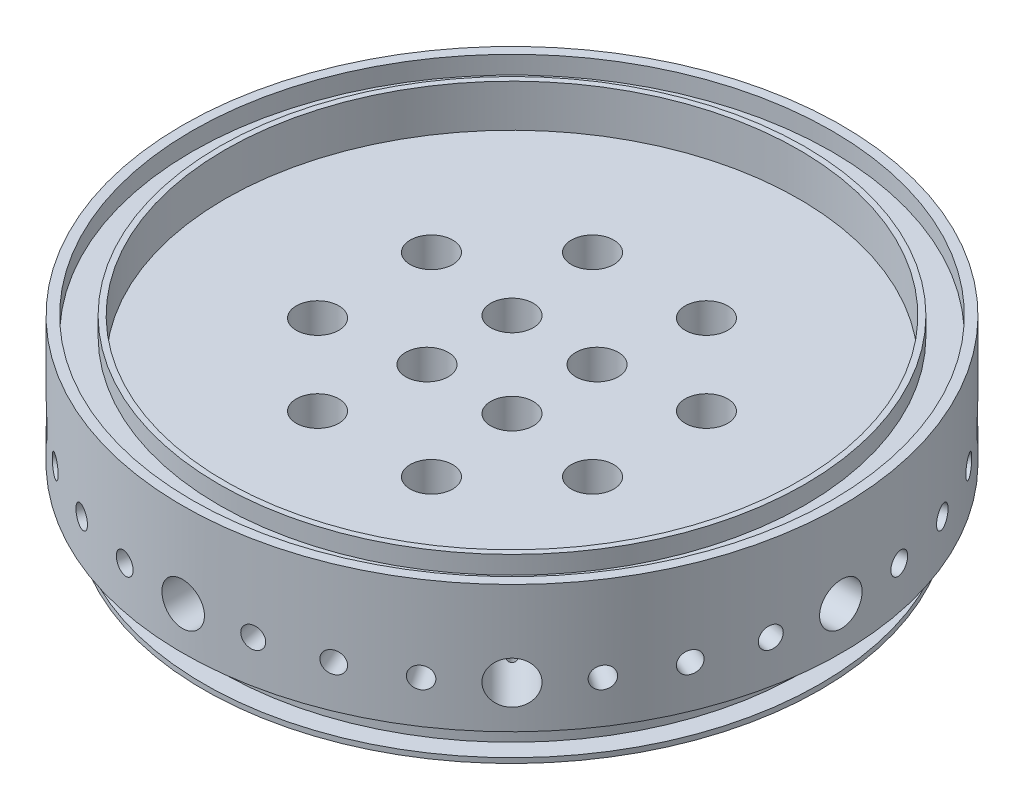
SolidWorks part; units mm, degrees
material "6061-T4 (SS)"
ref_plane "Front Plane" through (0, 0, 0) normal (0, 0, 1) x (1, 0, 0)
ref_plane "Top Plane" through (0, 0, 0) normal (0, 1, 0) x (1, 0, 0)
ref_plane "Right Plane" through (0, 0, 0) normal (1, 0, 0) x (0, 0, -1)
ref_axis "Axis1" through (0, -42.3, 0) along (0, 1, 0)
sketch "Sketch1" plane through (0, 0, 0) normal (0, 0, 1) x (1, 0, 0)
  line L0 (0, 0) -> (-46.0375, 0)
  line L1 (-46.0375, 0) -> (-46.0375, 0.7556)
  line L2 (-46.0375, 0.7556) -> (-43.2181, 0.7556)
  line L3 (-43.2181, 0.7556) -> (-43.2181, 5.5562)
  line L4 (-43.2181, 5.5562) -> (-46.0375, 5.5562)
  line L5 (-46.0375, 5.5562) -> (-46.0375, 6.35)
  line L6 (-46.0375, 6.35) -> (-49.2125, 6.35)
  line L7 (-49.2125, 6.35) -> (-49.2125, 25.4)
  line L10 (-42.8625, 19.05) -> (0, 19.05)
  line L11 (0, 19.05) -> (0, 0)
  line L12 (-42.8625, 19.05) -> (-42.8625, 25.4)
  line L15 (-49.2125, 25.4) -> (-47.7774, 25.4)
  line L16 (-47.7774, 25.4) -> (-47.7774, 22.7076)
  line L17 (-47.7774, 22.7076) -> (-43.7134, 22.7076)
  line L18 (-43.7134, 22.7076) -> (-43.7134, 25.4)
  line L19 (-43.7134, 25.4) -> (-42.8625, 25.4)
  dimension "D1" = 46.0375
  dimension "D2" = 4.8006
  dimension "D3" = 19.05
  dimension "D4" = 0.7937
  dimension "D6" = 3.175
  dimension "D7" = 6.35
  dimension "D9" = 19.05
  dimension "D10" = 4.064
  dimension "D11" = 2.6924
  dimension "D12" = 6.35
  dimension "o-ring -238" = 47.7774
  dimension "o-ring -" = 43.2181
revolve "Revolve1" add sketch "Sketch1" angle 360 about L11
ref_plane "Plane1" through (49.2125, 0, 0) normal (1, 0, 0) x (0, 0, -1)
hole_wizard "1/8 (0.125) Diameter Hole2" positions "Sketch36" profile "Sketch37" hole size "1/8" standard "ANSI Inch"
sketch "Sketch36" plane through (49.2125, 0, 0) normal (1, 0, 0) x (0, 0, -1)
  line L0 (0, 13.97) -> (0, -13.97) construction
  point P0 (0, 12.7)
  dimension "D1" = 12.7
sketch "Sketch37" plane through (49.2125, 12.7, 0) normal (0, 1, 0) x (0, 0, -1)
  line L0 (0, 0) -> (0, 13.6539)
  line L1 (0, 13.6539) -> (1.5875, 12.7)
  line L2 (1.5875, 12.7) -> (1.5875, 0)
  line L5 (1.5875, 0) -> (0, 0)
  line L10 (0, 13.6539) -> (-1.5875, 12.7) construction
  line L11 (0, -6.35) -> (0, 107.95) construction
  dimension "Hole Dia." = 3.175
  dimension "Hole Depth" = 12.7
  dimension "Drill Angle" = 118
pattern_circular "CirPattern9" count 32 over 360 about axis through (0, -42.3, 0) along (0, 1, 0) of "1/8 (0.125) Diameter Hole2"
hole_wizard "1/4 (0.25) Diameter Hole1" positions "Sketch12" profile "Sketch13" hole size "1/4" standard "ANSI Inch"
sketch "Sketch12" plane through (49.2125, 0, 0) normal (1, 0, 0) x (0, 0, -1)
  point P0 (0, 12.7)
  dimension "D1" = 12.7
sketch "Sketch13" plane through (49.2125, 12.7, 0) normal (0, 1, 0) x (0, 0, -1)
  line L0 (0, 0) -> (0, 14.6077)
  line L1 (0, 14.6077) -> (3.175, 12.7)
  line L2 (3.175, 12.7) -> (3.175, 0)
  line L5 (3.175, 0) -> (0, 0)
  line L10 (0, 14.6077) -> (-3.175, 12.7) construction
  line L11 (0, -6.35) -> (0, 107.95) construction
  dimension "Hole Dia." = 6.35
  dimension "Hole Depth" = 12.7
  dimension "Drill Angle" = 118
hole_wizard "3/16 (0.1875) Diameter Hole1" positions "Sketch14" profile "Sketch15" hole size "3/16" standard "ANSI Inch"
sketch "Sketch14" plane through (49.2125, 0, 0) normal (1, 0, 0) x (0, 0, -1)
  point P0 (0, 12.7)
sketch "Sketch15" plane through (49.2125, 12.7, 0) normal (0, 1, 0) x (0, 0, -1)
  line L0 (0, 0) -> (0, 33.1808)
  line L1 (0, 33.1808) -> (2.3812, 31.75)
  line L2 (2.3812, 31.75) -> (2.3812, 0)
  line L5 (2.3812, 0) -> (0, 0)
  line L10 (0, 33.1808) -> (-2.3813, 31.75) construction
  line L11 (0, -6.35) -> (0, 107.95) construction
  dimension "Hole Dia." = 4.7625
  dimension "Hole Depth" = 31.75
  dimension "Drill Angle" = 118
hole_wizard "1/8 (0.125) Diameter Hole1" positions "Sketch16" profile "Sketch17" hole size "1/8" standard "ANSI Inch"
sketch "Sketch16" plane through (49.2125, 0, 0) normal (1, 0, 0) x (0, 0, -1)
  point P0 (0, 12.7)
sketch "Sketch17" plane through (49.2125, 12.7, 0) normal (0, 1, 0) x (0, 0, -1)
  line L0 (0, 0) -> (0, 45.4039)
  line L1 (0, 45.4039) -> (1.5875, 44.45)
  line L2 (1.5875, 44.45) -> (1.5875, 0)
  line L5 (1.5875, 0) -> (0, 0)
  line L10 (0, 45.4039) -> (-1.5875, 44.45) construction
  line L11 (0, -6.35) -> (0, 107.95) construction
  dimension "Hole Dia." = 3.175
  dimension "Hole Depth" = 44.45
  dimension "Drill Angle" = 118
pattern_circular "CirPattern1" count 8 over 360 about axis through (0, -42.3, 0) along (0, 1, 0) of "1/4 (0.25) Diameter Hole1"
pattern_circular "CirPattern2" count 8 over 360 about axis through (0, -42.3, 0) along (0, 1, 0) of "3/16 (0.1875) Diameter Hole1"
pattern_circular "CirPattern3" count 4 over 360 about axis through (0, -42.3, 0) along (0, 1, 0) of "1/8 (0.125) Diameter Hole1"
ref_plane "Plane2" through (0, 19.05, 0) normal (0, 1, 0) x (1, 0, 0)
hole_wizard "inner large LOX holes" positions "Sketch19" profile "Sketch20" hole size "1/4" standard "ANSI Inch"
sketch "Sketch19" plane through (0, 19.05, 0) normal (0, 1, 0) x (1, 0, 0)
  line L2 (-6.35, 0) -> (0, 0) construction
  line L4 (-6.35, -6.35) -> (-6.35, 0) construction
  point P0 (-6.35, -6.35)
  dimension "D1" = 6.35
  dimension "D2" = 6.35
sketch "Sketch20" plane through (-6.35, 19.05, 6.35) normal (1, 0, 0) x (0, 0, 1)
  line L0 (0, 0) -> (0, 14.6077)
  line L1 (0, 14.6077) -> (3.175, 12.7)
  line L2 (3.175, 12.7) -> (3.175, 0)
  line L5 (3.175, 0) -> (0, 0)
  line L10 (0, 14.6077) -> (-3.175, 12.7) construction
  line L11 (0, -6.35) -> (0, 107.95) construction
  dimension "Hole Dia." = 6.35
  dimension "Hole Depth" = 12.7
  dimension "Drill Angle" = 118
hole_wizard "outer large LOX hole" positions "Sketch21" profile "Sketch22" hole size "1/4" standard "ANSI Inch"
sketch "Sketch21" plane through (0, 19.05, 0) normal (0, 1, 0) x (1, 0, 0)
  line L0 (-20.5332, -8.5051) -> (0, 0) construction
  line L2 (0, 0) -> (-17.5003, 0) construction
  point P0 (-20.5332, -8.5051)
  dimension "D1" = 22.5
  dimension "D2" = 22.225
sketch "Sketch22" plane through (-20.5332, 19.05, 8.5051) normal (1, 0, 0) x (0, 0, 1)
  line L0 (0, 0) -> (0, 14.6077)
  line L1 (0, 14.6077) -> (3.175, 12.7)
  line L2 (3.175, 12.7) -> (3.175, 0)
  line L5 (3.175, 0) -> (0, 0)
  line L10 (0, 14.6077) -> (-3.175, 12.7) construction
  line L11 (0, -6.35) -> (0, 107.95) construction
  dimension "Hole Dia." = 6.35
  dimension "Hole Depth" = 12.7
  dimension "Drill Angle" = 118
pattern_circular "CirPattern4" count 4 over 360 about axis through (0, -42.3, 0) along (0, 1, 0) of "inner large LOX holes"
pattern_circular "CirPattern5" count 8 over 360 about axis through (0, -42.3, 0) along (0, 1, 0) of "outer large LOX hole"
ref_plane "Plane4" through (-41.275, 0, 0) normal (1, 0, 0) x (0, 0, -1)
ref_axis "Axis4" through (-41.275, 0, -54.1338) along (0, 0, 1)
ref_plane "Plane5" through (-0.3135, -3.5837, 0) normal (0.0872, 0.9962, 0) x (0, 0, 1)
ref_plane "Plane6" through (-0.4519, -5.1651, 0) normal (0.0872, 0.9962, 0) x (0, 0, 1)
hole_wizard "film cooling holes" positions "Sketch25" profile "Sketch26" hole size "#74" standard "ANSI Inch"
sketch "Sketch25" plane through (-0.4519, -5.1651, 0) normal (0.0872, 0.9962, 0) x (0, 0, 1)
  line L0 (0, -41.1179) -> (0, 0) construction
  line L1 (-54.1338, -41.1179) -> (54.1338, -41.1179) construction
  point P0 (0, -41.1179)
sketch "Sketch26" plane through (-41.4134, -1.5815, 0) normal (0, 0, 1) x (0.9962, -0.0872, 0)
  line L0 (0, 0) -> (0, 12.8717)
  line L1 (0, 12.8717) -> (0.2857, 12.7)
  line L2 (0.2857, 12.7) -> (0.2857, 0)
  line L5 (0.2857, 0) -> (0, 0)
  line L10 (0, 12.8717) -> (-0.2858, 12.7) construction
  line L11 (0, -6.35) -> (0, 107.95) construction
  dimension "Hole Dia." = 0.5715
  dimension "Hole Depth" = 12.7
  dimension "Drill Angle" = 118
pattern_circular "CirPattern6" count 32 over 360 about axis through (0, -42.3, 0) along (0, 1, 0) of "film cooling holes"
hole_wizard "3/64 (0.04688) Diameter Hole1" positions "Sketch38" profile "Sketch39" hole size "3/64" standard "ANSI Inch"
sketch "Sketch38" plane through (-0.4519, -5.1651, 0) normal (0.0872, 0.9962, 0) x (0, 0, 1)
  point P0 (0, -41.1179)
sketch "Sketch39" plane through (-41.4134, -1.5815, 0) normal (0, 0, 1) x (0.9962, -0.0872, 0)
  line L0 (0, 0) -> (0, 13.0577)
  line L1 (0, 13.0577) -> (0.5954, 12.7)
  line L2 (0.5954, 12.7) -> (0.5954, 0)
  line L5 (0.5954, 0) -> (0, 0)
  line L10 (0, 13.0577) -> (-0.5954, 12.7) construction
  line L11 (0, -6.35) -> (0, 107.95) construction
  dimension "Hole Dia." = 1.1908
  dimension "Hole Depth" = 12.7
  dimension "Drill Angle" = 118
pattern_circular "CirPattern10" count 8 over 360 about axis through (0, -42.3, 0) along (0, 1, 0) of "3/64 (0.04688) Diameter Hole1"
hole_wizard "1/16 (0.0625) Diameter Hole2" positions "Sketch27" profile "Sketch28" hole size "1/16" standard "ANSI Inch"
sketch "Sketch27" plane through (0, 0, 0) normal (0, 1, 0) x (1, 0, 0)
  point P0 (-6.35, 0)
  dimension "D1" = 6.35
sketch "Sketch28" plane through (-6.35, 0, 0) normal (1, 0, 0) x (0, 0, -1)
  line L0 (0, 0) -> (0, 13.1769)
  line L1 (0, 13.1769) -> (0.7937, 12.7)
  line L2 (0.7937, 12.7) -> (0.7937, 0)
  line L5 (0.7937, 0) -> (0, 0)
  line L10 (0, 13.1769) -> (-0.7938, 12.7) construction
  line L11 (0, -6.35) -> (0, 107.95) construction
  dimension "Hole Dia." = 1.5875
  dimension "Hole Depth" = 12.7
  dimension "Drill Angle" = 118
ref_axis "Axis2" through (0, 19.05, -88.99) along (0, 0, 1)
ref_axis "Axis3" through (2.4606, 19.05, 0) along (-1, 0, 0)
ref_plane "impinging plane" through (0, -6.35, 0) normal (0, -1, 0) x (-1, 0, 0)
ref_axis "Axis5" through (-53.7659, -6.35, 0) along (1, 0, 0)
ref_plane "Plane8" through (0, -4.7625, -2.7496) normal (0, -0.866, -0.5) x (1, 0, 0)
hole_wizard "1/16 (0.0625) Diameter Hole1" positions "Sketch31" profile "Sketch30" hole size "1/16" standard "ANSI Inch"
sketch "Sketch31" plane through (0, -4.7625, -2.7496) normal (0, -0.866, -0.5) x (1, 0, 0)
  line L0 (-53.7659, 3.175) -> (54.5016, 3.175) construction
  point P0 (-6.35, 3.175)
  dimension "D1" = 6.35
sketch "Sketch30" plane through (-6.35, -6.35, 0) normal (1, 0, 0) x (0, 0.5, -0.866)
  line L0 (0, 0) -> (0, 16.0979)
  line L1 (0, 16.0979) -> (0.7937, 15.621)
  line L2 (0.7937, 15.621) -> (0.7937, 0)
  line L5 (0.7937, 0) -> (0, 0)
  line L10 (0, 16.0979) -> (-0.7938, 15.621) construction
  line L11 (0, -6.35) -> (0, 107.95) construction
  dimension "Hole Dia." = 1.5875
  dimension "Hole Depth" = 15.621
  dimension "Drill Angle" = 118
hole_wizard "1/16 (0.0625) Diameter Hole3" positions "Sketch32" profile "Sketch33" hole size "1/16" standard "ANSI Inch"
sketch "Sketch32" plane through (0, 0, 0) normal (0, 1, 0) x (1, 0, 0)
  point P0 (-22.225, 0)
  dimension "D1" = 22.225
sketch "Sketch33" plane through (-22.225, 0, 0) normal (1, 0, 0) x (0, 0, -1)
  line L0 (0, 0) -> (0, 13.1769)
  line L1 (0, 13.1769) -> (0.7937, 12.7)
  line L2 (0.7937, 12.7) -> (0.7937, 0)
  line L5 (0.7937, 0) -> (0, 0)
  line L10 (0, 13.1769) -> (-0.7938, 12.7) construction
  line L11 (0, -6.35) -> (0, 107.95) construction
  dimension "Hole Dia." = 1.5875
  dimension "Hole Depth" = 12.7
  dimension "Drill Angle" = 118
hole_wizard "1/16 (0.0625) Diameter Hole4" positions "Sketch34" profile "Sketch35" hole size "1/16" standard "ANSI Inch"
sketch "Sketch34" plane through (0, -4.7625, -2.7496) normal (0, -0.866, -0.5) x (1, 0, 0)
  line L0 (-53.7659, 3.175) -> (54.5016, 3.175) construction
  point P0 (-22.225, 3.175)
  dimension "D1" = 22.225
sketch "Sketch35" plane through (-22.225, -6.35, 0) normal (1, 0, 0) x (0, 0.5, -0.866)
  line L0 (0, 0) -> (0, 19.5269)
  line L1 (0, 19.5269) -> (0.7937, 19.05)
  line L2 (0.7937, 19.05) -> (0.7937, 0)
  line L5 (0.7937, 0) -> (0, 0)
  line L10 (0, 19.5269) -> (-0.7938, 19.05) construction
  line L11 (0, -6.35) -> (0, 107.95) construction
  dimension "Hole Dia." = 1.5875
  dimension "Hole Depth" = 19.05
  dimension "Drill Angle" = 118
mirror "Mirror1" about plane through (0, 0, 0) normal (0, 0, 1) of "1/16 (0.0625) Diameter Hole1"
mirror "Mirror2" about plane through (0, 0, 0) normal (0, 0, 1) of "1/16 (0.0625) Diameter Hole4"
pattern_circular "CirPattern7" count 4 over 360 about axis through (0, -42.3, 0) along (0, 1, 0) of "1/16 (0.0625) Diameter Hole1", "Mirror1", "1/16 (0.0625) Diameter Hole2"
pattern_circular "CirPattern8" count 8 over 360 about axis through (0, -42.3, 0) along (0, 1, 0) of "Mirror2", "1/16 (0.0625) Diameter Hole4", "1/16 (0.0625) Diameter Hole3"
